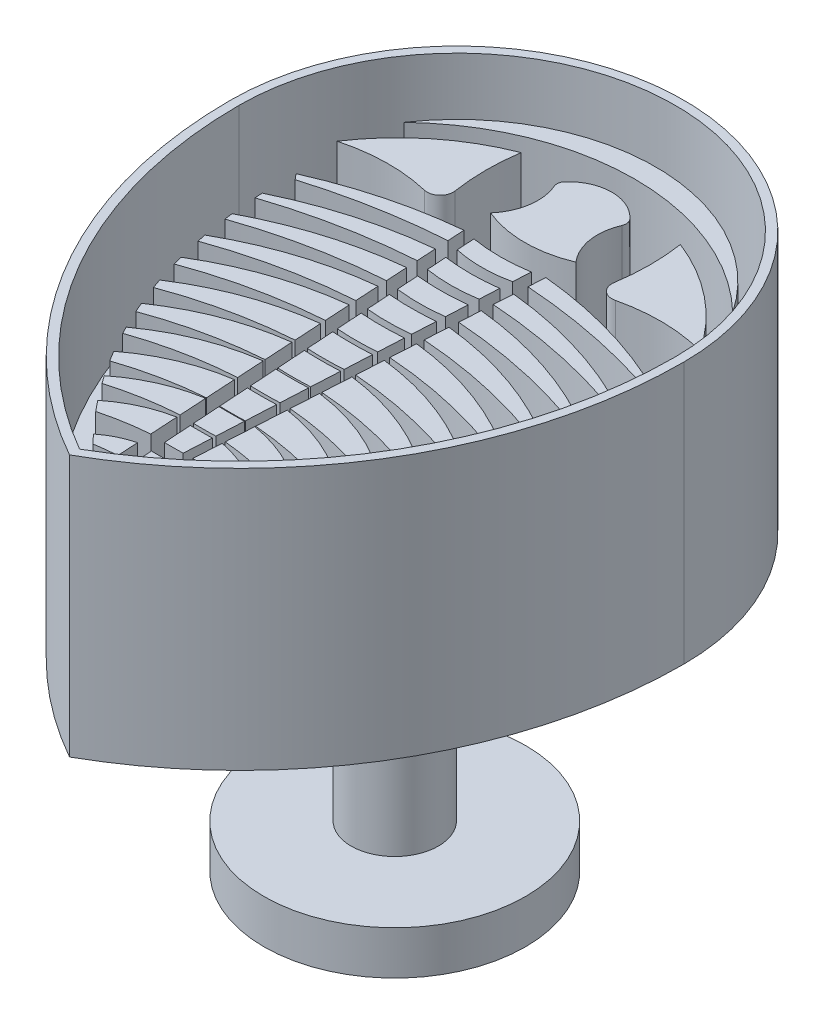
SolidWorks part; units mm, degrees
ref_plane "Přední rovina" through (0, 0, 0) normal (0, 0, 1) x (1, 0, 0)
ref_plane "Horní rovina" through (0, 0, 0) normal (0, 1, 0) x (1, 0, 0)
ref_plane "Pravá rovina" through (0, 0, 0) normal (1, 0, 0) x (0, 0, -1)
sketch "Skica1" plane through (0, 0, 0) normal (0, 1, 0) x (1, 0, 0)
  arc A0 (5, 0) -> (-5, 0) centre (0, 0) ccw
  arc A1 (-5, 0) -> (0, -8.6603) centre (5, 0) ccw
  arc A2 (0, -8.6603) -> (5, 0) centre (-5, 0) ccw
  dimension "D1" = 10
extrude "Přidat vysunutím1" add sketch "Skica1" against normal blind 3
sketch "Skica2" plane through (0, 0, 0) normal (0, 1, 0) x (1, 0, 0)
  line L0 (-0.9396, 1.0946) -> (-0.9163, 0.7054)
  line L1 (0.9396, 1.0946) -> (0.9163, 0.7054)
  line L2 (-0.4639, -6.8657) -> (-0.435, -7.3481)
  line L3 (-0.521, -5.9092) -> (-0.4831, -6.5437)
  line L4 (0.521, -5.9092) -> (0.4831, -6.5437)
  line L5 (-0.5631, -5.2058) -> (-0.5258, -5.8294)
  line L6 (-0.605, -4.5041) -> (-0.5642, -5.1865)
  line L7 (0.605, -4.5041) -> (0.5642, -5.1865)
  line L8 (0.6469, -3.8031) -> (0.6088, -4.4409)
  line L9 (-0.6469, -3.8031) -> (-0.6097, -4.4257)
  line L10 (-0.6887, -3.1028) -> (-0.6498, -3.7549)
  line L11 (0.6887, -3.1028) -> (0.6498, -3.7549)
  line L12 (0.7306, -2.4028) -> (0.6935, -3.0231)
  line L13 (-0.7306, -2.4028) -> (-0.6935, -3.0231)
  line L14 (-0.7724, -1.703) -> (-0.7376, -2.2844)
  line L15 (0.7724, -1.703) -> (0.7376, -2.2844)
  line L16 (0.8142, -1.0034) -> (0.7821, -1.5408)
  line L17 (-0.8142, -1.0034) -> (-0.7821, -1.5408)
  line L18 (-0.856, -0.304) -> (-0.8267, -0.7938)
  line L19 (0.856, -0.304) -> (0.8267, -0.7938)
  line L20 (0.8978, 0.3954) -> (0.8715, -0.0448)
  line L21 (-0.8978, 0.3954) -> (-0.8715, -0.0448)
  line L22 (0.4639, -6.8657) -> (0.434, -7.3648)
  line L23 (0.5631, -5.2058) -> (0.5249, -5.8452)
  line L24 (-0.6539, 1.0367) -> (-0.6272, 0.6279)
  line L25 (0.6621, 1.0381) -> (0.641, 0.6309)
  line L26 (-0.6089, 0.3483) -> (-0.5795, -0.1033)
  line L27 (0.6264, 0.3507) -> (0.6031, -0.0994)
  line L28 (0.5906, -0.3401) -> (0.5649, -0.8356)
  line L29 (-0.5638, -0.3429) -> (-0.5314, -0.8398)
  line L30 (0.5547, -1.0329) -> (0.5266, -1.5735)
  line L31 (-0.5186, -1.0361) -> (-0.4832, -1.5778)
  line L32 (-0.4732, -1.7307) -> (-0.4351, -2.3147)
  line L33 (0.5186, -1.7274) -> (0.4884, -2.3105)
  line L34 (-0.4279, -2.4264) -> (-0.3873, -3.0482)
  line L35 (0.4826, -2.4231) -> (0.4504, -3.0442)
  line L36 (-0.3369, -3.8204) -> (-0.2962, -4.4435)
  line L37 (0.4103, -3.8173) -> (0.378, -4.4401)
  line L38 (0.4464, -3.1197) -> (0.4126, -3.7721)
  line L39 (-0.3824, -3.123) -> (-0.3398, -3.7759)
  line L40 (0.3377, -5.2158) -> (0.3054, -5.8391)
  line L41 (-0.2456, -5.2184) -> (-0.205, -5.8419)
  line L42 (0.374, -4.5159) -> (0.3387, -5.1981)
  line L43 (-0.2913, -4.5188) -> (-0.2468, -5.2012)
  line L44 (-0.1999, -5.9198) -> (-0.1585, -6.554)
  line L45 (0.3013, -5.9174) -> (0.2685, -6.5517)
  line L46 (-0.1376, -6.874) -> (-0.1061, -7.3562)
  line L47 (0.2518, -6.8721) -> (0.2268, -7.3544)
  arc A0 (3.7723, 2.5471) -> (-3.7723, 2.5471) centre (0, 0) ccw
  arc A1 (3.7723, 2.5471) -> (-3.7723, 2.5471) centre (0, -1.3616) ccw
  arc A2 (-1.826, 3.293) -> (-4.1627, 1.4083) centre (0, -1.3616) ccw
  arc A7 (4.1627, 1.4083) -> (2.1882, 1.4375) centre (3.118, -2.4529) ccw
  arc A8 (-1.826, 3.293) -> (-1.8221, 1.7756) centre (3.118, 2.5471) ccw
  arc A9 (4.1627, 1.4083) -> (1.826, 3.293) centre (0, -1.3616) ccw
  arc A10 (1.8221, 1.7756) -> (1.826, 3.293) centre (-3.118, 2.5471) ccw
  arc A11 (-2.1882, 1.4375) -> (-1.8221, 1.7756) centre (-2.1185, 1.7293) ccw
  arc A12 (1.8221, 1.7756) -> (2.1882, 1.4375) centre (2.1185, 1.7293) ccw
  arc A13 (-2.1882, 1.4375) -> (-4.1627, 1.4083) centre (-3.118, -2.4529) ccw
  arc A15 (-0.9784, 1.7445) -> (-0.778, 3.0046) centre (-1.8819, 2.5341) ccw
  arc A16 (0.778, 3.0046) -> (0.9784, 1.7445) centre (1.8819, 2.5341) ccw
  arc A17 (-0.7425, 3.2169) -> (-0.778, 3.0046) centre (-0.594, 3.083) ccw
  arc A18 (0.778, 3.0046) -> (0.7425, 3.2169) centre (0.594, 3.083) ccw
  arc A20 (3.996, 0.288) -> (0.9396, 1.0946) centre (0, -8.6603) ccw
  arc A21 (-0.9784, 1.7445) -> (0.9784, 1.7445) centre (0, 4.0705) ccw
  arc A22 (0.7425, 3.2169) -> (-0.7425, 3.2169) centre (0, 2.5471) ccw
  arc A23 (3.989, -0.4811) -> (0.8978, 0.3954) centre (0, -8.6603) ccw
  arc A24 (3.9271, -1.2348) -> (0.856, -0.304) centre (0, -8.6603) ccw
  arc A25 (3.8134, -1.9708) -> (0.8142, -1.0034) centre (0, -8.6603) ccw
  arc A26 (3.6503, -2.6874) -> (0.7724, -1.703) centre (0, -8.6603) ccw
  arc A27 (3.4403, -3.3825) -> (0.7306, -2.4028) centre (0, -8.6603) ccw
  arc A28 (3.1856, -4.0546) -> (0.6887, -3.1028) centre (0, -8.6603) ccw
  arc A29 (2.8883, -4.702) -> (0.6469, -3.8031) centre (0, -8.6603) ccw
  arc A30 (2.5505, -5.3234) -> (0.605, -4.5041) centre (0, -8.6603) ccw
  arc A31 (2.1739, -5.9172) -> (0.5631, -5.2058) centre (0, -8.6603) ccw
  arc A32 (1.76, -6.4825) -> (0.521, -5.9092) centre (0, -8.6603) ccw
  arc A33 (1.1422, -7.2005) -> (0.4639, -6.8657) centre (0, -8.6603) ccw
  arc A34 (-4.9974, -0.2302) -> (0, -8.6603) centre (5, 0) ccw
  arc A35 (0, -8.6603) -> (4.9974, -0.2302) centre (-5, 0) ccw
  arc A36 (3.9992, 0.1259) -> (0.9163, 0.7054) centre (0, -12.6603) ccw
  arc A37 (3.9794, -0.6572) -> (0.8715, -0.0448) centre (0, -12.6603) ccw
  arc A38 (3.903, -1.4236) -> (0.8267, -0.7938) centre (0, -12.6603) ccw
  arc A39 (3.773, -2.1713) -> (0.7821, -1.5408) centre (0, -12.6603) ccw
  arc A40 (3.5921, -2.8981) -> (0.7376, -2.2844) centre (0, -12.6603) ccw
  arc A41 (3.3628, -3.6022) -> (0.6935, -3.0231) centre (0, -12.6603) ccw
  arc A42 (3.0872, -4.2819) -> (0.6498, -3.7549) centre (0, -12.6603) ccw
  arc A43 (2.7721, -4.9273) -> (0.6088, -4.4409) centre (-0.103, -12.6603) ccw
  arc A44 (2.4059, -5.5618) -> (0.5642, -5.1865) centre (0, -12.6603) ccw
  arc A45 (2.01, -6.1506) -> (0.5249, -5.8452) centre (-0.103, -12.6603) ccw
  arc A46 (1.5622, -6.7269) -> (0.4831, -6.5437) centre (0, -12.6603) ccw
  arc A47 (0.9136, -7.4357) -> (0.434, -7.3648) centre (-0.103, -12.6603) ccw
  arc A51 (0.9136, -7.4357) -> (1.1422, -7.2005) centre (-6.5, 0) ccw
  arc A52 (-0.9396, 1.0946) -> (-3.996, 0.288) centre (0, -8.6603) ccw
  arc A53 (-1.1422, -7.2005) -> (-0.9445, -7.4046) centre (6.5, 0) ccw
  arc A54 (-1.76, -6.4825) -> (-1.5622, -6.7269) centre (6.5, 0) ccw
  arc A55 (-2.1739, -5.9172) -> (-2.0475, -6.0984) centre (6.5, 0) ccw
  arc A56 (-2.5505, -5.3234) -> (-2.4059, -5.5618) centre (6.5, 0) ccw
  arc A57 (-2.8883, -4.702) -> (-2.8049, -4.8651) centre (6.5, 0) ccw
  arc A58 (-3.1856, -4.0546) -> (-3.0872, -4.2819) centre (6.5, 0) ccw
  arc A59 (-3.4403, -3.3825) -> (-3.3628, -3.6022) centre (6.5, 0) ccw
  arc A60 (-3.6503, -2.6874) -> (-3.5921, -2.8981) centre (6.5, 0) ccw
  arc A61 (-3.8134, -1.9708) -> (-3.773, -2.1713) centre (6.5, 0) ccw
  arc A62 (-3.9271, -1.2348) -> (-3.903, -1.4236) centre (6.5, 0) ccw
  arc A63 (-3.989, -0.4811) -> (-3.9794, -0.6572) centre (6.5, 0) ccw
  arc A64 (3.9992, 0.1259) -> (3.996, 0.288) centre (-6.5, 0) ccw
  arc A65 (3.9794, -0.6572) -> (3.989, -0.4811) centre (-6.5, 0) ccw
  arc A66 (3.903, -1.4236) -> (3.9271, -1.2348) centre (-6.5, 0) ccw
  arc A67 (3.773, -2.1713) -> (3.8134, -1.9708) centre (-6.5, 0) ccw
  arc A68 (3.5921, -2.8981) -> (3.6503, -2.6874) centre (-6.5, 0) ccw
  arc A69 (3.3628, -3.6022) -> (3.4403, -3.3825) centre (-6.5, 0) ccw
  arc A70 (3.0872, -4.2819) -> (3.1856, -4.0546) centre (-6.5, 0) ccw
  arc A71 (2.7721, -4.9273) -> (2.8883, -4.702) centre (-6.5, 0) ccw
  arc A72 (2.4059, -5.5618) -> (2.5505, -5.3234) centre (-6.5, 0) ccw
  arc A73 (2.01, -6.1506) -> (2.1739, -5.9172) centre (-6.5, 0) ccw
  arc A74 (1.5622, -6.7269) -> (1.76, -6.4825) centre (-6.5, 0) ccw
  arc A75 (-0.9163, 0.7054) -> (-3.9992, 0.1259) centre (0, -12.6603) ccw
  arc A76 (-0.8978, 0.3954) -> (-3.989, -0.4811) centre (0, -8.6603) ccw
  arc A77 (-0.8715, -0.0448) -> (-3.9794, -0.6572) centre (0, -12.6603) ccw
  arc A78 (-0.856, -0.304) -> (-3.9271, -1.2348) centre (0, -8.6603) ccw
  arc A79 (-0.8267, -0.7938) -> (-3.903, -1.4236) centre (0, -12.6603) ccw
  arc A80 (-0.8142, -1.0034) -> (-3.8134, -1.9708) centre (0, -8.6603) ccw
  arc A81 (-0.7821, -1.5408) -> (-3.773, -2.1713) centre (0, -12.6603) ccw
  arc A82 (-0.7724, -1.703) -> (-3.6503, -2.6874) centre (0, -8.6603) ccw
  arc A83 (-0.7376, -2.2844) -> (-3.5921, -2.8981) centre (0, -12.6603) ccw
  arc A84 (-0.7306, -2.4028) -> (-3.4403, -3.3825) centre (0, -8.6603) ccw
  arc A85 (-0.6935, -3.0231) -> (-3.3628, -3.6022) centre (0, -12.6603) ccw
  arc A86 (-0.6887, -3.1028) -> (-3.1856, -4.0546) centre (0, -8.6603) ccw
  arc A87 (-0.6498, -3.7549) -> (-3.0872, -4.2819) centre (0, -12.6603) ccw
  arc A88 (-0.6469, -3.8031) -> (-2.8883, -4.702) centre (0, -8.6603) ccw
  arc A89 (-0.6097, -4.4257) -> (-2.8049, -4.8651) centre (-0.103, -12.6603) ccw
  arc A90 (-0.605, -4.5041) -> (-2.5505, -5.3234) centre (0, -8.6603) ccw
  arc A91 (-0.5642, -5.1865) -> (-2.4059, -5.5618) centre (0, -12.6603) ccw
  arc A92 (-0.5631, -5.2058) -> (-2.1739, -5.9172) centre (0, -8.6603) ccw
  arc A93 (-0.5258, -5.8294) -> (-2.0475, -6.0984) centre (-0.103, -12.6603) ccw
  arc A94 (-0.521, -5.9092) -> (-1.76, -6.4825) centre (0, -8.6603) ccw
  arc A95 (-0.4831, -6.5437) -> (-1.5622, -6.7269) centre (0, -12.6603) ccw
  arc A96 (-0.4639, -6.8657) -> (-1.1422, -7.2005) centre (0, -8.6603) ccw
  arc A97 (-0.435, -7.3481) -> (-0.9445, -7.4046) centre (-0.103, -12.6603) ccw
  arc A98 (-3.996, 0.288) -> (-3.9992, 0.1259) centre (6.5, 0) ccw
  arc A100 (5, 0) -> (-5, 0) centre (0, 0) ccw construction
  arc A108 (-0.2913, -4.5188) -> (0.374, -4.5159) centre (0, 5) ccw
  arc A111 (-0.1376, -6.874) -> (0.2518, -6.8721) centre (0, 5) ccw
  arc A112 (-0.6539, 1.0367) -> (0.6621, 1.0381) centre (0, 5) ccw
  arc A113 (-0.5186, -1.0361) -> (0.5547, -1.0329) centre (0, 5) ccw
  arc A114 (-0.4732, -1.7307) -> (0.5186, -1.7274) centre (0, 5) ccw
  arc A115 (-0.5795, -0.1033) -> (0.6031, -0.0994) centre (0, 3.5471) ccw
  arc A116 (-0.6089, 0.3483) -> (0.6264, 0.3507) centre (0, 5) ccw
  arc A117 (-0.5638, -0.3429) -> (0.5906, -0.3401) centre (0, 5) ccw
  arc A118 (-0.4279, -2.4264) -> (0.4826, -2.4231) centre (0, 5) ccw
  arc A119 (-0.4351, -2.3147) -> (0.4884, -2.3105) centre (0, 3.5471) ccw
  arc A120 (-0.3873, -3.0482) -> (0.4504, -3.0442) centre (0, 3.5471) ccw
  arc A121 (-0.3824, -3.123) -> (0.4464, -3.1197) centre (0, 5) ccw
  arc A122 (-0.3369, -3.8204) -> (0.4103, -3.8173) centre (0, 5) ccw
  arc A123 (-0.1999, -5.9198) -> (0.3013, -5.9174) centre (0, 5) ccw
  arc A124 (-0.2456, -5.2184) -> (0.3377, -5.2158) centre (0, 5) ccw
  arc A125 (-0.1585, -6.554) -> (0.2685, -6.5517) centre (0, 3.5471) ccw
  arc A129 (-3.9876, 0.2918) -> (-3.8789, 0.163) centre (0, 3.5471) ccw
  arc A134 (-0.2468, -5.2012) -> (0.3387, -5.1981) centre (0, 3.5471) ccw
  arc A138 (-0.6272, 0.6279) -> (0.641, 0.6309) centre (0, 3.5471) ccw
  arc A139 (-0.4832, -1.5778) -> (0.5266, -1.5735) centre (0, 3.5471) ccw
  arc A140 (-0.2962, -4.4435) -> (0.378, -4.4401) centre (0, 3.5471) ccw
  arc A141 (-0.5314, -0.8398) -> (0.5649, -0.8356) centre (0, 3.5471) ccw
  arc A142 (-0.3398, -3.7759) -> (0.4126, -3.7721) centre (0, 3.5471) ccw
  arc A143 (-0.205, -5.8419) -> (0.3054, -5.8391) centre (0, 3.5471) ccw
  arc A144 (-0.1061, -7.3562) -> (0.2268, -7.3544) centre (0, 3.5471) ccw
  point P44 (0, -12.6603)
  point P176 (0, 0)
  dimension "D1" = 4
  dimension "D4" = 1.5
  dimension "D5" = 1.5
extrude "Přidat vysunutím2" add sketch "Skica2" along normal blind 2 contours A97 L2 A96 A53 | A95 L3 A94 A54 | A93 L5 A92 A55 | A91 L6 A90 A56 | A89 L9 A88 A57 | A87 L10 A86 A58 | A85 L13 A84 A59 | A83 L14 A82 A60 | A81 L17 A80 A61 | A77 L21 A76 A63 | A52 A129 A75 L0 | A13 A11 A8 A2 | A1 A0 | A18 A22 A17 A15 A21 A16 | A10 A12 A7 A9 | L24 A138 L25 A112 | A116 L26 A115 L27 | L29 A141 L28 A117 | L31 A139 L30 A113 | L32 A119 L33 A114 | L34 A120 L35 A118 | L39 A142 L38 A121 | L36 A140 L37 A122 | L43 A134 L42 A108 | L41 A143 L40 A124 | L44 A125 L45 A123 | L46 A144 L47 A111 | A47 A51 A33 L22 | A46 A74 A32 L4 | A45 A73 A31 L23 | A44 A72 A30 L7 | A43 A71 A29 L8 | A42 A70 A28 L11 | A41 A69 A27 L12 | A40 A68 A26 L15 | A39 A67 A25 L16 | A38 A66 A24 L19 | A37 A65 A23 L20 | A84 A59 A85 L13 | A78 A62 A79 L18 | A36 L1 A20 A64 region at (-2.2521, 0, -0.6787) region at (-0.7289, 0, 7.169) region at (-1.0328, 0, 6.351) region at (1.0328, 0, 6.351) region at (-1.2291, 0, 5.6712) region at (-1.4297, 0, 5.0378) region at (1.4297, 0, 5.0378) region at (1.6079, 0, 4.3464) region at (-1.5774, 0, 4.3173) region at (-1.7578, 0, 3.6642) region at (1.7578, 0, 3.6642) region at (1.8946, 0, 2.9605) region at (-1.8946, 0, 2.9605) region at (-2.0121, 0, 2.2477) region at (2.0121, 0, 2.2477) region at (2.1095, 0, 1.527) region at (-2.1095, 0, 1.527) region at (2.1859, 0, 0.7993) region at (2.2402, 0, 0.0656) region at (-2.2402, 0, 0.0656) region at (0.728, 0, 7.1802) region at (1.2436, 0, 5.6936) region at (0.0053, 0, -0.7937) region at (0.0101, 0, -0.0961) region at (0.0149, 0, 0.6092) region at (0.0198, 0, 1.3186) region at (0.0246, 0, 2.0295) region at (0.0294, 0, 2.7402) region at (0.0387, 0, 4.13) region at (0.0341, 0, 3.4492) region at (0.0481, 0, 5.5244) region at (0.0436, 0, 4.8548) region at (0.0528, 0, 6.229) region at (0.0587, 0, 7.1089) region at (0, 0, -4.1486) region at (-2.6742, 0, -2.1513) region at (2.6742, 0, -2.1513) region at (0, 0, -2.4956)
extrude "Vysunout tenkostěnný1" add sketch "Skica1<2>" along normal mid plane 6 separate body thin thin type one direction wall 0.2
sketch "Skica1<2>" plane through (0, 0, 0) normal (0, 1, 0) x (1, 0, 0) same geometry as "Skica1"
ref_plane "Rovina1" through (0, -3, 0) normal (0, -1, 0) x (-1, 0, 0)
sketch "Skica4" plane through (0, -3, 0) normal (0, -1, 0) x (-1, 0, 0)
  circle A0 centre (0, -1.4317) radius 1
  point P10 (0, -1.4317)
  dimension "D1" = 2
extrude "Přidat vysunutím3" add sketch "Skica4" along normal blind 5
ref_plane "Rovina2" through (0, -8, 0) normal (0, -1, 0) x (-1, 0, 0)
sketch "Skica5" plane through (0, -8, 0) normal (0, -1, 0) x (-1, 0, 0)
  circle A0 centre (0, -1.4317) radius 3
  dimension "D1" = 6
extrude "Přidat vysunutím4" add sketch "Skica5" along normal blind 1
